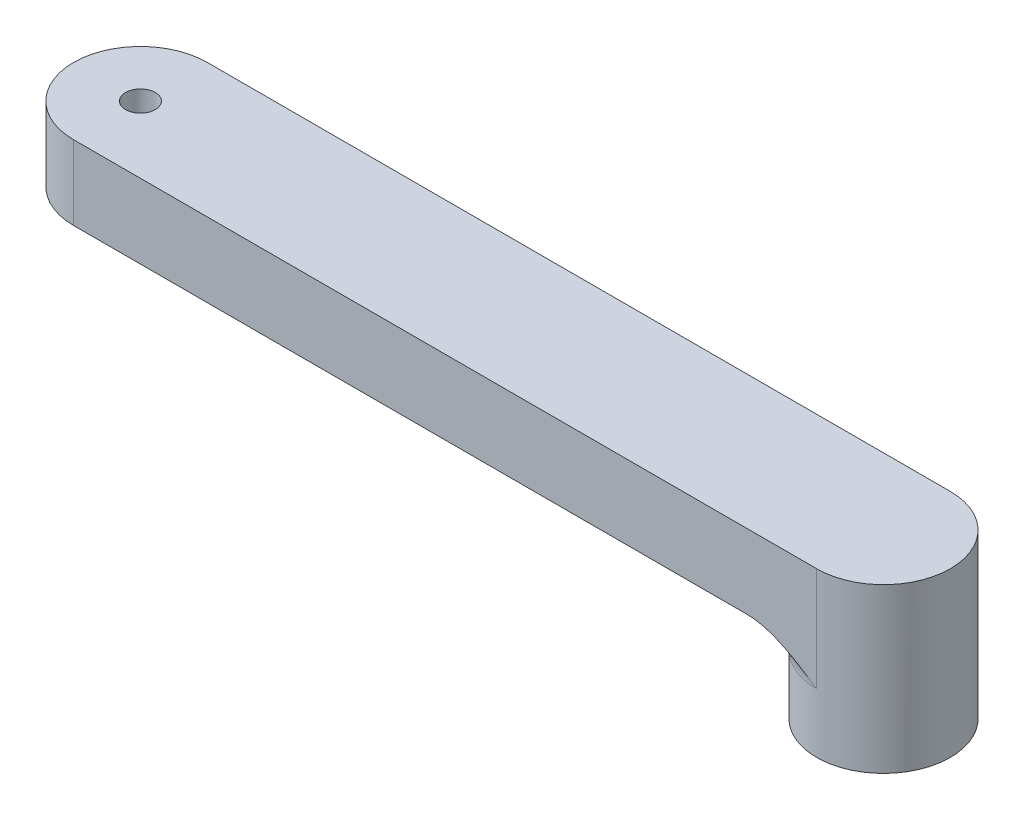
SolidWorks part; units mm, degrees
ref_plane "Front Plane" through (0, 0, 0) normal (0, 0, 1) x (1, 0, 0)
ref_plane "Top Plane" through (0, 0, 0) normal (0, 1, 0) x (1, 0, 0)
ref_plane "Right Plane" through (0, 0, 0) normal (1, 0, 0) x (0, 0, -1)
sketch "Sketch1" plane through (0, 0, 0) normal (0, 1, 0) x (1, 0, 0)
  line L0 (14.9142, 0.6009) -> (38992.301, 0.6009) construction
  line L1 (0, 0) -> (0, 38977.3867) construction
  line L2 (-15.875, 3.4584) -> (15.875, 3.4584)
  line L4 (-15.875, -2.2566) -> (15.875, -2.2566)
  arc A0 (-15.875, 3.4584) -> (-15.875, -2.2566) centre (-15.875, 0.6009) ccw
  arc A1 (15.875, 3.4584) -> (15.875, -2.2566) centre (15.875, 0.6009) cw
  point P9 (0, 3.4584)
  point P13 (0, -2.2566)
  dimension "0.225" = 5.715
  dimension "D2" = 31.75
extrude "Boss-Extrude1" add sketch "Sketch1" along normal blind 3.175
sketch "Sketch2" plane through (0, 0, 0) normal (0, -1, 0) x (1, 0, 0)
  circle A0 centre (15.875, -0.6009) radius 1.905
  circle A6 centre (15.875, -0.6009) radius 2.8575
  arc A7 (15.875, -3.4584) -> (15.875, 2.2566) centre (15.875, -0.6009) ccw construction
  arc A8 (15.875, -3.4584) -> (15.875, 2.2566) centre (15.875, -0.6009) ccw construction
  arc A9 (-15.875, 2.2566) -> (-15.875, -3.4584) centre (-15.875, -0.6009) ccw construction
  arc A10 (-15.875, 2.2566) -> (-15.875, -3.4584) centre (-15.875, -0.6009) ccw construction
  dimension "D2" = 3.81
extrude "Boss-Extrude2" add sketch "Sketch2" along normal blind 3.81
fillet "Fillet1" radius 1.27 1 edges at (13.0175, 0, -0.6009)
sketch "Sketch3" plane through (0, 0, 0) normal (0, -1, 0) x (1, 0, 0)
  circle A0 centre (-15.875, -0.6009) radius 0.635
  point P3 (0, 0)
  dimension "D1" = 1.27
extrude "Cut-Extrude1" cut sketch "Sketch3" against normal through all
